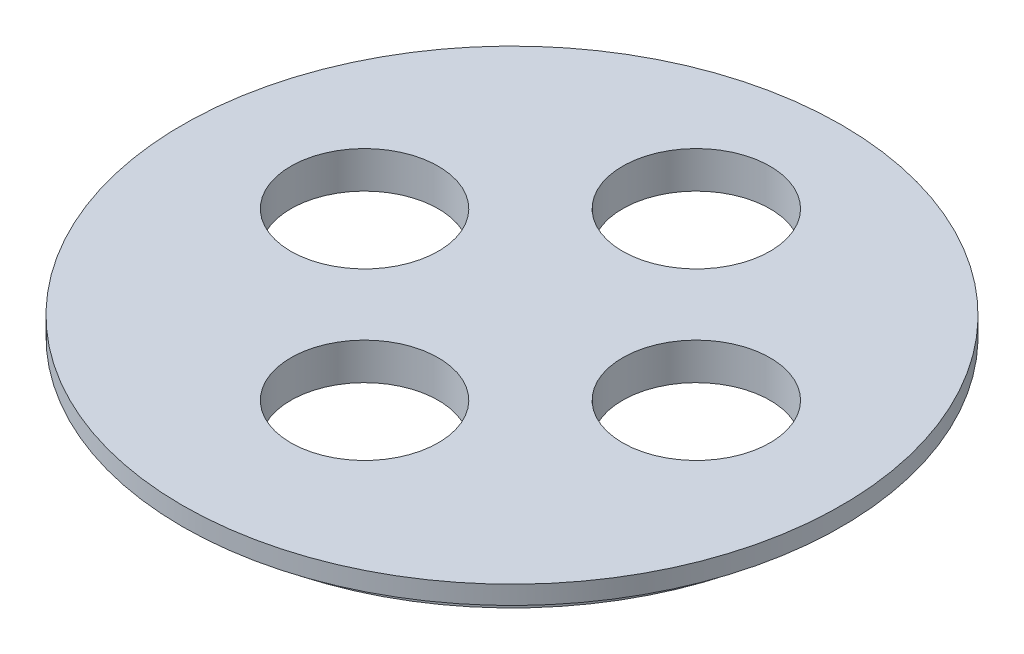
SolidWorks part; units mm, degrees
ref_plane "Front Plane" through (0, 0, 0) normal (0, 0, 1) x (1, 0, 0)
ref_plane "Top Plane" through (0, 0, 0) normal (0, 1, 0) x (1, 0, 0)
ref_plane "Right Plane" through (0, 0, 0) normal (1, 0, 0) x (0, 0, -1)
sketch "Sketch1" plane through (0, 0, 0) normal (0, 1, 0) x (1, 0, 0)
  circle A0 centre (0, 0) radius 56.769
  circle A1 centre (0, 0) radius 52.8002
  dimension "D1" = 113.538
  dimension "D2" = 3.9688
extrude "Boss-Extrude1" add sketch "Sketch1" along normal blind 3.175 contours A1 | A0 A1 region at (-55.1633, 0, 0) region at (0, 0, 0)
extrude "Boss-Extrude2" add sketch "Sketch1<3>" against normal blind 3.175 contours A1 region at (0, 0, 0)
sketch "Sketch1<3>" plane through (0, 0, 0) normal (0, 1, 0) x (1, 0, 0) same geometry as "Sketch1"
sketch "Sketch2" plane through (0, 3.175, 0) normal (0, 1, 0) x (1, 0, 0)
  circle A0 centre (0, 31.75) radius 12.7
  circle A1 centre (28.575, 3.175) radius 12.7
  circle A2 centre (0, -25.4) radius 12.7
  circle A3 centre (-28.575, 3.175) radius 12.7
  dimension "D1" = 25.4
  dimension "D2" = 31.75
  dimension "D3" = 4
extrude "Cut-Extrude1" cut sketch "Sketch2" against normal through all
